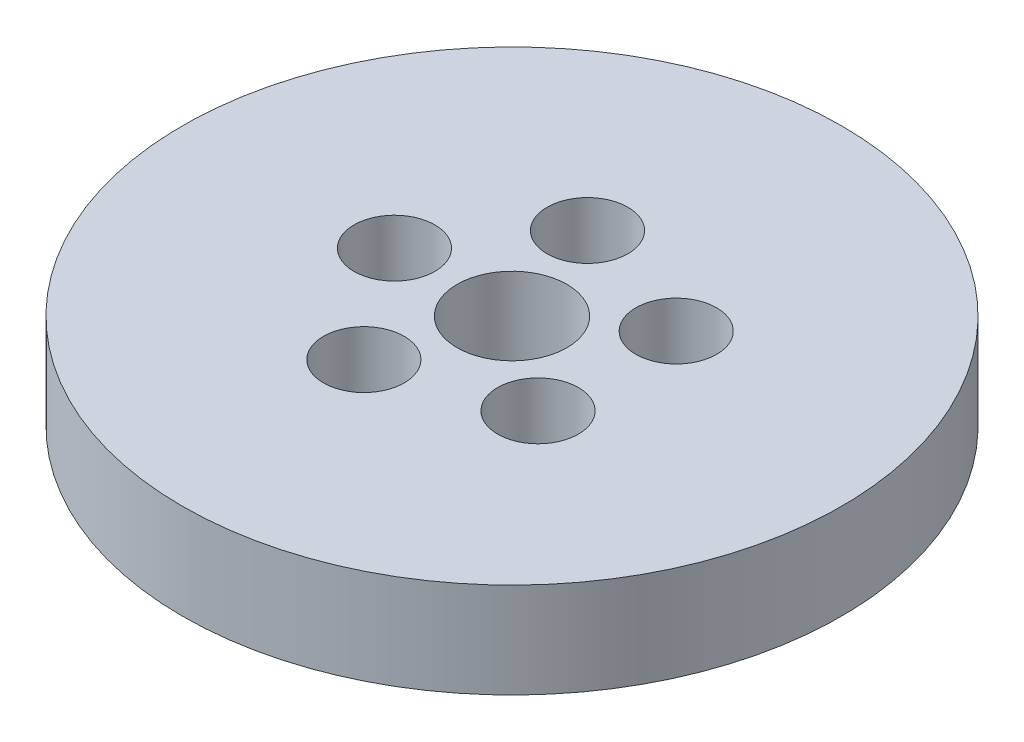
SolidWorks part; units mm, degrees
ref_plane "Front Plane" through (0, 0, 0) normal (0, 0, 1) x (1, 0, 0)
ref_plane "Top Plane" through (0, 0, 0) normal (0, 1, 0) x (1, 0, 0)
ref_plane "Right Plane" through (0, 0, 0) normal (1, 0, 0) x (0, 0, -1)
sketch "Sketch1" plane through (0, 0, 0) normal (0, 1, 0) x (1, 0, 0)
  circle A0 centre (0, 0) radius 45
  dimension "FLANGE_OD" = 90
extrude "Boss-Extrude1" add sketch "Sketch1" along normal blind 13
sketch "Sketch2" plane through (0, 0, 0) normal (0, 1, 0) x (1, 0, 0)
  circle A0 centre (0, 0) radius 7.5
  dimension "BORE_D" = 15
extrude "Cut-Extrude1" cut sketch "Sketch2" along normal through all
sketch "Sketch3" plane through (0, 13, 0) normal (0, 1, 0) x (1, 0, 0)
  circle A0 centre (0, 0) radius 16.0538 construction
  circle A1 centre (-16.0538, 0) radius 5.5147
  dimension "BOLT_D" = 11.0295
  dimension "BOLT_PCD" = 32.1076
extrude "Cut-Extrude2" cut sketch "Sketch3" against normal blind 8.1173
pattern_circular "CirPattern1" count 5 over 360 about axis through (0, 0, 0) along (0, 1, 0) of "Cut-Extrude2"
